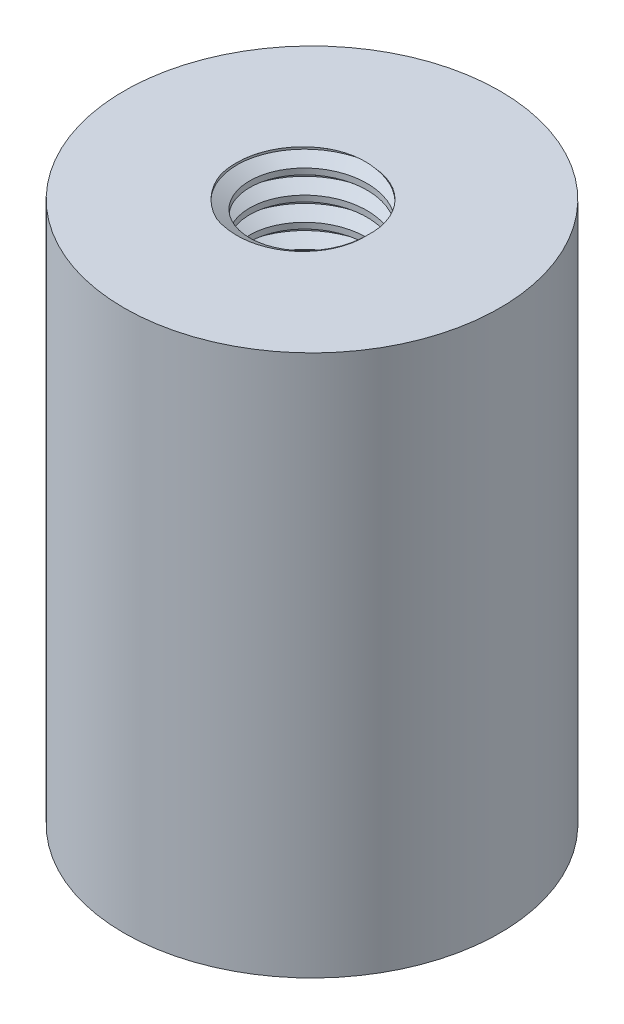
SolidWorks part; units mm, degrees
ref_plane "Front Plane" through (0, 0, 0) normal (0, 0, 1) x (1, 0, 0)
ref_plane "Top Plane" through (0, 0, 0) normal (0, 1, 0) x (1, 0, 0)
ref_plane "Right Plane" through (0, 0, 0) normal (1, 0, 0) x (0, 0, -1)
sketch "Sketch1" plane through (0, 0, 0) normal (0, 1, 0) x (1, 0, 0)
  circle A0 centre (0, 0) radius 6.35
  dimension "D1" = 12.7
extrude "Boss-Extrude1" add sketch "Sketch1" along normal blind 18.288
sketch "Sketch13" plane through (0, 18.288, 0) normal (0, 1, 0) x (1, 0, 0)
  circle A0 centre (0, 0) radius 1.9844
  dimension "D1" = 3.9688
extrude "Cut-Extrude1" cut sketch "Sketch13" against normal blind 20.574
thread "Thread1" pitch 0.7937 method cut profile "Thread Profile3" start angle 0, offset 1, length 0, pitch 0.7937, diameter 3.9688
ref_plane "Plane3" through (-1.9844, 19.288, 0) normal (0, 0, 1) x (-1, 0, 0)
sketch "Thread Profile3" plane through (-1.9844, 19.288, 0) normal (0, 0, 1) x (-1, 0, 0)
  line L0 (0, 0) -> (0, 0.7937) construction
  line L1 (0, 0) -> (0.4296, 0.248)
  line L2 (0.4296, 0.248) -> (0.4296, 0.3473)
  line L3 (0.4296, 0.3473) -> (0, 0.5953)
  line L4 (0.4296, 0.2977) -> (0, 0.2977) construction
  line L11 (0, 0) -> (0, 0.5953)
  point P2 (0, 0)
  dimension "Pitch" = 0.7937
  dimension "Profile_Angle" = 60
  dimension "Profile_Land" = 0.0992
  dimension "Profile_Height" = 0.4296
